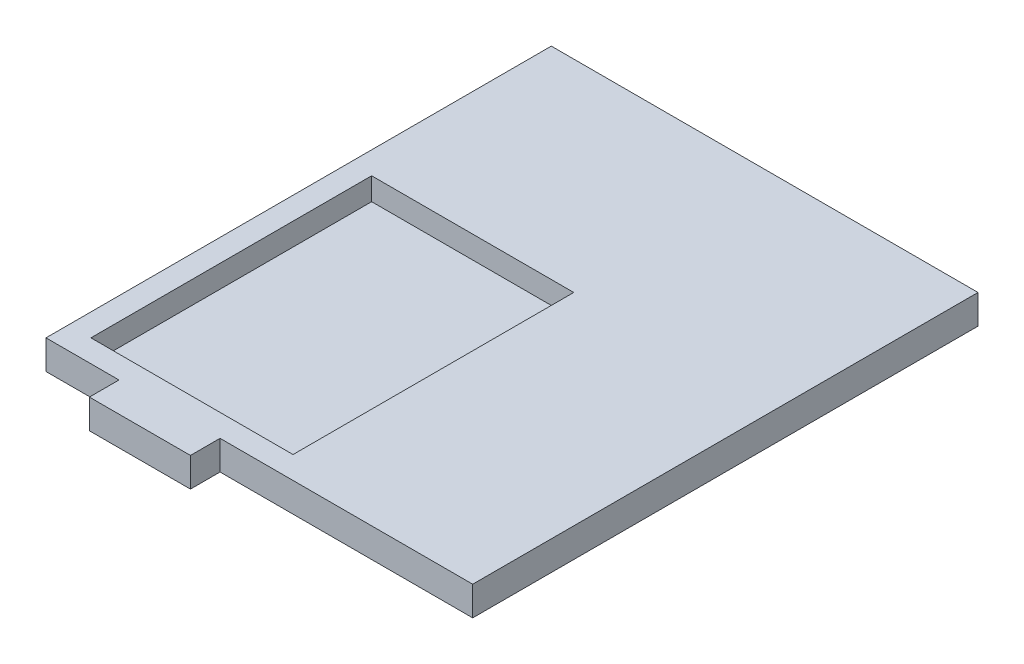
SolidWorks part; units mm, degrees
ref_plane "Front Plane" through (0, 0, 0) normal (0, 0, 1) x (1, 0, 0)
ref_plane "Top Plane" through (0, 0, 0) normal (0, 1, 0) x (1, 0, 0)
ref_plane "Right Plane" through (0, 0, 0) normal (1, 0, 0) x (0, 0, -1)
sketch "Sketch1" plane through (0, 0, 0) normal (0, 1, 0) x (1, 0, 0)
  line L0 (45, 0) -> (45, -23.1837) construction
  line L1 (0, 0) -> (90, 0)
  line L2 (0, 0) -> (0, 125)
  line L3 (0, 125) -> (90, 125)
  line L4 (90, 0) -> (90, 125)
  line L5 (-10, -10) -> (180, -10)
  line L6 (-10, -10) -> (-10, 215)
  line L7 (-10, 215) -> (180, 215)
  line L8 (180, -10) -> (180, 215)
  line L9 (22.5, -10) -> (67.5, -10)
  line L10 (22.5, -10) -> (22.5, -23.1837)
  line L11 (22.5, -23.1837) -> (67.5, -23.1837)
  line L12 (67.5, -10) -> (67.5, -23.1837)
  point P15 (0, 0)
  point P16 (45, -23.1837)
  dimension "D1" = 90
  dimension "D2" = 125
  dimension "D3" = 10
  dimension "D4" = 10
  dimension "D5" = 90
  dimension "D6" = 90
  dimension "D7" = 45
extrude "Boss-Extrude1" add sketch "Sketch1" against normal blind 3 contours L1 L4 L3 L2 | L5 L8 L7 L6 L4 L1 L2 L3 | L2 L1 L4 L3 | L6 L5 L8 L7 | L10 L9 L12 L11 region at (45, 0, -62.5) region at (99.2857, 0, -116.7857)
extrude "Boss-Extrude2" add sketch "Sketch1<3>" along normal blind 10 contours L4 L1 L9 L5 L8 L7 L6 L2 L3 | L0 L5 L10 L11 | L9 L0 L11 L12 region at (99.2857, 0, -116.7857) region at (56.25, 0, 16.5918) region at (33.75, 0, 16.5918)
sketch "Sketch1<3>" plane through (0, 0, 0) normal (0, 1, 0) x (1, 0, 0) same geometry as "Sketch1"
